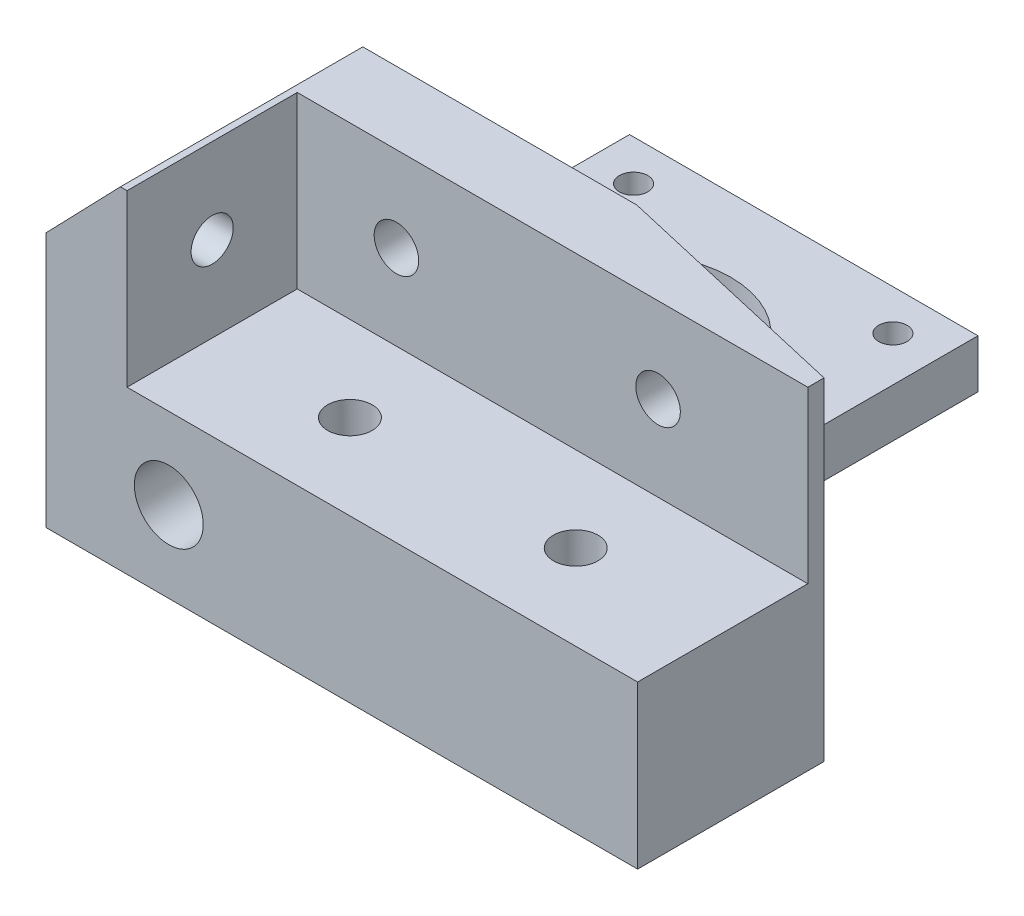
SolidWorks part; units mm, degrees
ref_plane "Спереди" through (0, 0, 0) normal (0, 0, 1) x (1, 0, 0)
ref_plane "Сверху" through (0, 0, 0) normal (0, 1, 0) x (1, 0, 0)
ref_plane "Справа" through (0, 0, 0) normal (1, 0, 0) x (0, 0, -1)
sketch "Эскиз1" plane through (0, 0, 0) normal (0, 1, 0) x (1, 0, 0)
  line L0 (-31.7371, -43.025) -> (41.2629, -43.025)
  line L1 (-31.7371, 28.975) -> (11.2629, 28.975)
  line L2 (-31.7371, 28.975) -> (-31.7371, -43.025)
  line L4 (11.2629, 28.975) -> (11.2629, -13.1094)
  line L5 (41.2629, -43.025) -> (41.2629, -20.025)
  line L6 (55.066, 26.975) -> (55.066, -15.1094) construction
  line L7 (41.2629, -20.025) -> (11.2629, -13.1094)
  line L8 (-39.7831, 7.975) -> (-39.7831, 23.975) construction
  line L9 (-10.2371, 36.7685) -> (-26.2371, 36.7685) construction
  circle A0 centre (-10.2371, 7.975) radius 12
  circle A1 centre (-26.2371, 23.975) radius 1.75
  circle A2 centre (5.7629, 23.975) radius 1.75
  circle A3 centre (5.7629, -8.025) radius 1.75
  circle A4 centre (-26.2371, -8.025) radius 1.75
  dimension "D1" = 16
  dimension "D3" = 3.5
  dimension "D2" = 16
  dimension "D4" = 2
  dimension "D5" = 2
extrude "Бобышка-Вытянуть1" add sketch "Эскиз1" along normal blind 6
sketch "Эскиз2" plane through (0, 6, 0) normal (0, 1, 0) x (1, 0, 0)
  line L0 (41.2629, -20.025) -> (11.2629, -13.1094)
  line L1 (11.2629, -13.1094) -> (-31.7371, -13.1094)
  line L2 (-31.7371, 28.975) -> (-31.7371, -43.025) construction
  line L3 (-31.7371, -13.1094) -> (-31.7371, -43.025)
  line L4 (-31.7371, -43.025) -> (41.2629, -43.025)
  line L5 (41.2629, -43.025) -> (41.2629, -20.025)
extrude "Бобышка-Вытянуть2" add sketch "Эскиз2" along normal blind 35
sketch "Эскиз3" plane through (0, 41, 0) normal (0, 1, 0) x (1, 0, 0)
  line L1 (41.2629, -43.025) -> (-21.7371, -43.025)
  line L2 (41.2629, -43.025) -> (41.2629, -22.025)
  line L3 (41.2629, -22.025) -> (-21.7371, -22.025)
  line L4 (-21.7371, -43.025) -> (-21.7371, -22.025)
  dimension "D1" = 21
  dimension "D2" = 63
extrude "Вырез-Вытянуть1" cut sketch "Эскиз3" against normal blind 21
sketch "Эскиз4" plane through (-21.7371, 0, 0) normal (1, 0, 0) x (0, 0, -1)
  circle A0 centre (-32.525, 30.5) radius 2.6
  dimension "D1" = 5.2
extrude "Вырез-Вытянуть2" cut sketch "Эскиз4" against normal through all
chamfer "Фаска1" distance 9.5 angle 44 1 edges at (-31.7371, 41, 28.0672) first distance on face at (-31.7371, 30.5, 29.925)
sketch "Эскиз5" plane through (-21.7371, 0, 0) normal (1, 0, 0) x (0, 0, -1)
  circle A0 centre (-32.525, 30.5) radius 4.25
  dimension "D1" = 8.5
extrude "Вырез-Вытянуть3" cut sketch "Эскиз5" along normal blind 5 from offset 10 offset against normal yes
sketch "Эскиз6" plane through (0, 0, 22.025) normal (0, 0, 1) x (1, 0, 0)
  circle A0 centre (-9.4957, 30.5) radius 2.75
  circle A1 centre (22.7857, 30.5) radius 2.75
  dimension "D1" = 5.5
  dimension "D2" = 5.5
extrude "Вырез-Вытянуть4" cut sketch "Эскиз6" against normal through all
sketch "Эскиз7" plane through (0, 0, 22.025) normal (0, 0, 1) x (1, 0, 0)
  circle A0 centre (-9.4957, 30.5) radius 4.25
  circle A1 centre (22.7857, 30.5) radius 4.25
  dimension "D1" = 8.5
  dimension "D2" = 8.5
extrude "Вырез-Вытянуть5" cut sketch "Эскиз7" against normal blind 5 from offset 4 offset against normal yes
sketch "Эскиз8" plane through (0, 20, 0) normal (0, 1, 0) x (1, 0, 0)
  circle A0 centre (-4.737, -32.525) radius 2.75
  circle A1 centre (23.1264, -32.525) radius 2.75
  dimension "D1" = 5.5
  dimension "D2" = 5.5
extrude "Вырез-Вытянуть6" cut sketch "Эскиз8" against normal through all
sketch "Эскиз10" plane through (0, 0, 0) normal (0, -1, 0) x (1, 0, 0)
  circle A0 centre (23.1264, 32.525) radius 4.25
  circle A1 centre (-4.737, 32.525) radius 4.25
  dimension "D1" = 8.5
  dimension "D2" = 8.5
extrude "Вырез-Вытянуть7" cut sketch "Эскиз10" against normal blind 15.5
sketch "Эскиз11" plane through (0, 0, 43.025) normal (0, 0, 1) x (1, 0, 0)
  line L0 (-21.7371, -2.4743) -> (-16.5871, -2.4743) construction
  circle A1 centre (-16.5871, 10) radius 4.25
  dimension "D3" = 8.5
  dimension "D2" = 5.15
extrude "Вырез-Вытянуть8" cut sketch "Эскиз11" against normal blind 20
ref_plane "Плоскость1" through (51.2629, 0, 0) normal (1, 0, 0) x (0, 0, -1)
